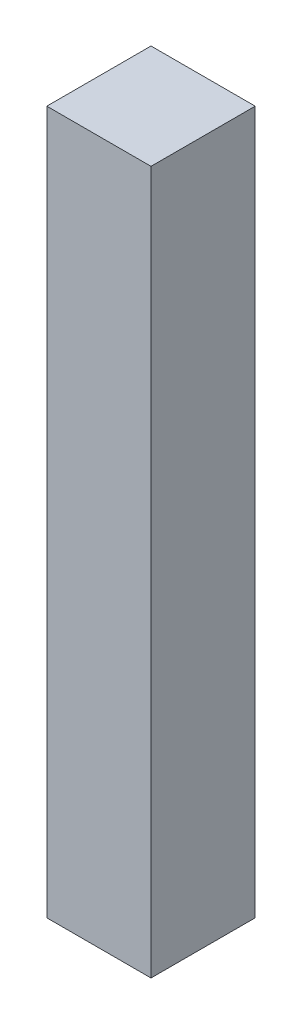
SolidWorks part; units mm, degrees
material "6061 Alloy"
ref_plane "Front Plane" through (0, 0, 0) normal (0, 0, 1) x (1, 0, 0)
ref_plane "Top Plane" through (0, 0, 0) normal (0, 1, 0) x (1, 0, 0)
ref_plane "Right Plane" through (0, 0, 0) normal (1, 0, 0) x (0, 0, -1)
sketch "Sketch1" plane through (0, 0, 0) normal (0, 1, 0) x (1, 0, 0)
  line L1 (-3.15, 3.15) -> (3.15, 3.15)
  line L2 (-3.15, 3.15) -> (-3.15, -3.15)
  line L3 (-3.15, -3.15) -> (3.15, -3.15)
  line L4 (3.15, 3.15) -> (3.15, -3.15)
  line L5 (-3.15, 3.15) -> (3.15, -3.15) construction
  line L6 (-3.15, -3.15) -> (3.15, 3.15) construction
  point P0 (0, 0)
  dimension "D1" = 6.3
extrude "Boss-Extrude1" add sketch "Sketch1" along normal blind 42.5
